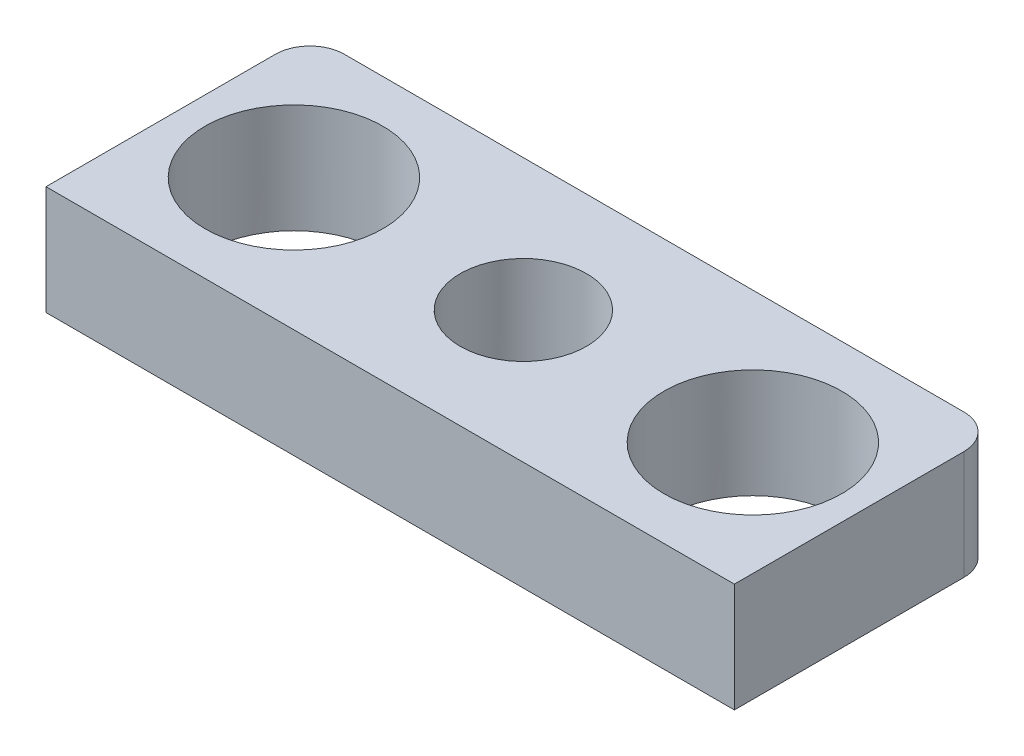
SolidWorks part; units mm, degrees
ref_plane "前视基准面" through (0, 0, 0) normal (0, 0, 1) x (1, 0, 0)
ref_plane "上视基准面" through (0, 0, 0) normal (0, 1, 0) x (1, 0, 0)
ref_plane "右视基准面" through (0, 0, 0) normal (1, 0, 0) x (0, 0, -1)
sketch "草图1" plane through (0, 0, 0) normal (0, 1, 0) x (1, 0, 0)
  line L0 (0, 0) -> (0, 22.9971) construction
  line L1 (0, 0) -> (0, -15) construction
  line L2 (0, 0) -> (-30, 0)
  line L4 (-30, 0) -> (-30, 23)
  line L5 (-30, 23) -> (-14, 23)
  line L6 (-14, 23) -> (-14, 22.9971)
  line L13 (-14, 22.9971) -> (14, 22.9971)
  line L14 (14, 22.9971) -> (14, 23)
  line L15 (14, 23) -> (30, 23)
  line L16 (30, 23) -> (30, 0)
  line L17 (30, 0) -> (0, 0)
  point P0 (0, 0)
  dimension "D1" = 30
  dimension "D3" = 23
  dimension "D4" = 16
extrude "凸台-拉伸1" add sketch "草图1" along normal blind 9.5
sketch "草图2" plane through (0, 9.5, 0) normal (0, 1, 0) x (1, 0, 0)
  line L0 (0.1102, 18.5459) -> (0.1102, 1.5459) construction
  line L1 (-21.8898, 1.5459) -> (22.1102, 1.5459) construction
  line L2 (14, 22.9971) -> (-14, 22.9971) construction
  line L3 (-30, 0) -> (30, 0) construction
  circle A0 centre (20.1102, 11.5) radius 7.75
  circle A1 centre (-19.8898, 11.5) radius 7.75
  circle A2 centre (0.1102, 11.4971) radius 5.5
  dimension "D1" = 15.5
  dimension "D2" = 40
  dimension "D3" = 11.5
  dimension "D4" = 11
  dimension "D5" = 11.5
fillet "圆角1" radius 3 4 edges at (30, 4.75, -23) (14, 4.75, -22.9971) (-14, 4.75, -22.9971) (-30, 4.75, -23)
extrude "切除-拉伸2" cut sketch "草图2" against normal blind 10
ref_plane "基准面1" through (0, 4.5, 0) normal (0, 1, 0) x (1, 0, 0)
sketch "草图5" plane through (0, 4.5, 0) normal (0, 1, 0) x (1, 0, 0)
  line L0 (9, 0) -> (9, 22.9971) construction
  line L1 (-30, 0) -> (30, 0) construction
  line L2 (13.8676, 22.9971) -> (-13.8676, 22.9971) construction
  line L3 (-9, 22.9971) -> (-9, 0) construction
  line L4 (30, 0) -> (30, 20) construction
  line L5 (-30, 20) -> (-30, 0) construction
  dimension "D1" = 21
  dimension "D2" = 21
